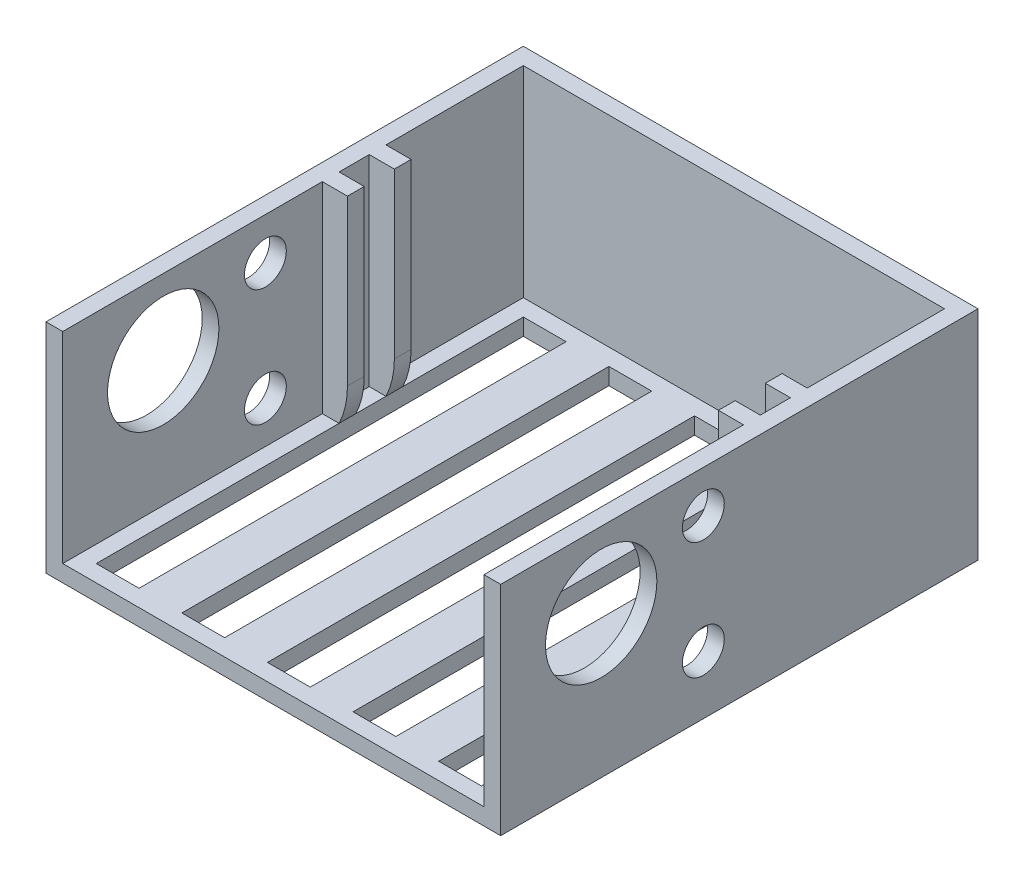
SolidWorks part; units mm, degrees
ref_plane "Alzado" through (0, 0, 0) normal (0, 0, 1) x (1, 0, 0)
ref_plane "Planta" through (0, 0, 0) normal (0, 1, 0) x (1, 0, 0)
ref_plane "Vista lateral" through (0, 0, 0) normal (1, 0, 0) x (0, 0, -1)
sketch "Croquis1" plane through (0, 0, 0) normal (0, 1, 0) x (1, 0, 0)
  line L0 (2, 2) -> (-52.3, 2)
  line L1 (0, 0) -> (-50.3, 0)
  line L2 (0, 0) -> (0, -55)
  line L3 (0, -55) -> (-50.3, -55)
  line L4 (-50.3, 0) -> (-50.3, -55)
  line L5 (-52.3, 2) -> (-52.3, -57)
  line L6 (2, -57) -> (-52.3, -57)
  line L7 (2, 2) -> (2, -57)
  dimension "D1" = 50.3
  dimension "D2" = 55
  dimension "D3" = 2
extrude "Saliente-Extruir1" add sketch "Croquis1" along normal blind 24
sketch "Croquis2" plane through (0, 0, 0) normal (0, -1, 0) x (1, 0, 0)
  line L4 (2, -2) -> (2, 57)
  line L5 (2, 57) -> (-52.3, 57)
  line L6 (-52.3, 57) -> (-52.3, -2)
  line L7 (-52.3, -2) -> (2, -2)
  line L8 (2, -2) -> (2, 57)
  line L9 (2, 57) -> (-52.3, 57)
  line L10 (-52.3, 57) -> (-52.3, -2)
  line L11 (-52.3, -2) -> (2, -2)
  dimension "D1" = 0
extrude "Saliente-Extruir2" add sketch "Croquis2" along normal blind 2
sketch "Croquis6" plane through (-52.3, 0, 0) normal (-1, 0, 0) x (0, 0, 1)
  line L0 (55, 24) -> (55, 0) construction
  line L1 (55, 24) -> (55, 0)
  line L2 (55, 0) -> (55, -2)
  line L3 (57, -2) -> (-2, -2) construction
  line L4 (55, -2) -> (57, -2)
  line L5 (57, -2) -> (57, 24)
  line L6 (57, 24) -> (55, 24)
extrude "Cortar-Extruir4" cut sketch "Croquis6" against normal up to surface (54.3 mm away) up to face at (2, 11, 27.5)
sketch "Croquis7" plane through (0, 0, 0) normal (0, 1, 0) x (1, 0, 0)
  line L10 (-43.1889, -2) -> (-43.1889, -53)
  line L11 (-38.0778, -2) -> (-38.0778, -53)
  line L12 (-32.9667, -2) -> (-32.9667, -53)
  line L13 (-27.8556, -2) -> (-27.8556, -53)
  line L14 (-2, -53) -> (-2, -2)
  line L15 (-2, -2) -> (-48.3, -2)
  line L16 (-48.3, -2) -> (-48.3, -53)
  line L17 (-48.3, -53) -> (-2, -53)
  line L18 (-2, -53) -> (-2, -2)
  line L19 (-2, -2) -> (-7.4111, -2)
  line L20 (-48.3, -2) -> (-48.3, -53)
  line L21 (-48.3, -53) -> (-43.1889, -53)
  line L22 (-22.7444, -2) -> (-22.7444, -53)
  line L23 (-17.6333, -2) -> (-17.6333, -53)
  line L24 (-12.5222, -2) -> (-12.5222, -53)
  line L25 (-7.4111, -2) -> (-7.4111, -53)
  line L26 (-2.3, -2) -> (-2.3, -53)
  line L27 (-48.3, -2) -> (-43.1889, -2)
  line L28 (-43.1889, -2) -> (-48.3, -2)
  line L29 (-38.0778, -53) -> (-32.9667, -53)
  line L30 (-27.8556, -53) -> (-22.7444, -53)
  line L31 (-17.6333, -53) -> (-12.5222, -53)
  line L32 (-7.4111, -53) -> (-2, -53)
  line L33 (-12.5222, -2) -> (-17.6333, -2)
  line L34 (-22.7444, -2) -> (-27.8556, -2)
  line L35 (-32.9667, -2) -> (-38.0778, -2)
  dimension "D3" = 5.1111
  dimension "D1" = 2
  dimension "D2" = 10
extrude "Cortar-Extruir5" cut sketch "Croquis7" against normal up to next contours L27 L20 L21 L10 | L12 L35 L11 L29 | L24 L33 L23 L31 | L25 L32 L18 L19 | L13 L30 L22 L34 region at (-45.7444, 0, 27.5) region at (-35.5222, 0, 27.5) region at (-15.0778, 0, 27.5) region at (-4.8556, 0, 27.5)
ref_plane "Plano1" through (-25.15, 0, 0) normal (1, 0, 0) x (0, 0, -1)
sketch "Croquis8" plane through (-25.15, 0, 0) normal (1, 0, 0) x (0, 0, -1)
  line L0 (0, 24) -> (-55, 24) construction
  line L1 (0, 24) -> (-55, 24) construction
  line L2 (0, 15) -> (-43, 15) construction
  line L4 (0, 15) -> (0, 24) construction
  line L6 (-49.65, 15) -> (-43, 15) construction
  circle A0 centre (-43, 15) radius 6.65
  dimension "D2" = 13.3
  dimension "D1" = 9
  dimension "D3" = 43
extrude "Cortar-Extruir6" cut sketch "Croquis8" against normal through all both and the other way through all
ref_plane "Plano2" through (-25.15, 0, 0) normal (1, 0, 0) x (0, 0, -1)
sketch "Croquis9" plane through (-25.15, 0, 0) normal (1, 0, 0) x (0, 0, -1)
  line L0 (-30.8, 19) -> (-30.8, 5) construction
  line L1 (-55, 24) -> (-55, 17.3891) construction
  line L4 (-55, 24) -> (-36, 24) construction
  line L5 (-36, 24) -> (-36, 19) construction
  line L6 (-36, 19) -> (-30.8, 19) construction
  line L7 (0, 0) -> (-55, 0) construction
  line L8 (0, 0) -> (-55, 0) construction
  line L9 (-30.8, 5) -> (-30.8, 0) construction
  circle A0 centre (-30.8, 19) radius 2.5
  circle A1 centre (-30.8, 5) radius 2.5
  dimension "D4" = 5
  dimension "D6" = 5
  dimension "D1" = 19
  dimension "D2" = 5
  dimension "D3" = 5.2
  dimension "D5" = 5
extrude "Cortar-Extruir7" cut sketch "Croquis9" against normal through all both and the other way through all
sketch "Croquis10" plane through (0, 24, 0) normal (0, 1, 0) x (1, 0, 0)
  line L0 (-50.3, -55) -> (-50.3, -22) construction
  line L1 (-50.3, 0) -> (-50.3, -55) construction
  line L2 (-50.3, -22) -> (-50.3, -18.4) construction
  line L3 (-50.3, -18.4) -> (-50.3, -16.4) construction
  line L4 (-50.3, -20.2) -> (-48.1828, -20.2) construction
  line L5 (-50.3, -18.4) -> (-47.3, -18.4)
  line L6 (-50.3, -18.4) -> (-50.3, -16.4)
  line L7 (-50.3, -16.4) -> (-47.3, -16.4)
  line L8 (-47.3, -18.4) -> (-47.3, -16.4)
  line L9 (-50.3, -22) -> (-50.3, -24)
  line L10 (-47.3, -22) -> (-47.3, -24)
  line L11 (-50.3, -24) -> (-47.3, -24)
  line L12 (-50.3, -22) -> (-47.3, -22)
  line L13 (-25.15, 0) -> (-25.15, -7.7827) construction
  line L14 (0, 0) -> (-50.3, 0) construction
  line L15 (0, -22) -> (-3, -22)
  line L16 (-3, -22) -> (-3, -24)
  line L17 (0, -24) -> (-3, -24)
  line L18 (0, -22) -> (0, -24)
  line L19 (0, -16.4) -> (-3, -16.4)
  line L20 (-3, -18.4) -> (-3, -16.4)
  line L21 (0, -18.4) -> (-3, -18.4)
  line L22 (0, -18.4) -> (0, -16.4)
  point P26 (0, 0)
  dimension "D1" = 33
  dimension "D2" = 3.6
  dimension "D3" = 2
  dimension "D4" = 3
extrude "Saliente-Extruir3" add sketch "Croquis10" against normal up to surface (24 mm away) up to face at (-15.0778, 0, 27.5)
fillet "Redondeo1" radius 10 4 edges at (-3, 0, 17.4) (-3, 0, 23) (-47.3, 0, 17.4) (-47.3, 0, 23)
